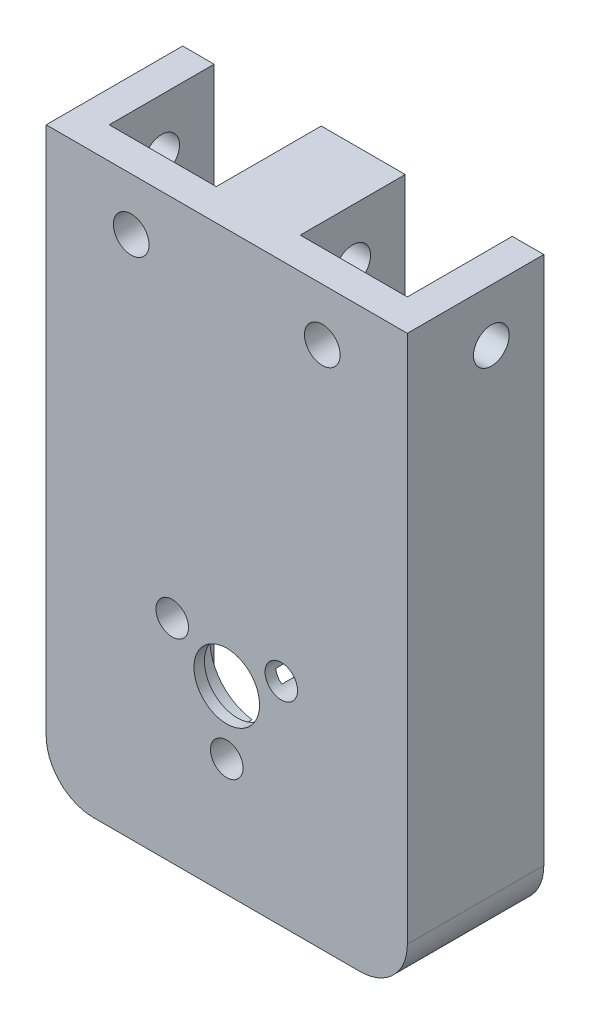
SolidWorks part; units mm, degrees
ref_plane "Front Plane" through (0, 0, 0) normal (0, 0, 1) x (1, 0, 0)
ref_plane "Top Plane" through (0, 0, 0) normal (0, 1, 0) x (1, 0, 0)
ref_plane "Right Plane" through (0, 0, 0) normal (1, 0, 0) x (0, 0, -1)
sketch "Sketch1" plane through (0, 0, 0) normal (0, 0, 1) x (1, 0, 0)
  line L0 (0, 20) -> (0, -20) construction
  line L1 (25, 0) -> (-25, 0) construction
  line L2 (17.2, 1.2765) -> (17.2, 37.7)
  line L3 (17.2, 37.7) -> (14.2, 37.7)
  line L4 (0, 37.7) -> (0, 14.7) construction
  line L5 (0, -14) -> (14.2, -14) construction
  line L6 (-14.2, -14.2) -> (14.2, -14.2)
  line L7 (-17.2, -17.2) -> (17.2, -17.2)
  line L8 (17.2, 1.2765) -> (17.2, -17.2)
  line L9 (14.2, 0) -> (14.2, -14.2)
  line L10 (0, -14) -> (25, -14) construction
  line L11 (0, -14.2) -> (25, -14.2) construction
  line L12 (0, -17.2) -> (25, -17.2) construction
  line L13 (-17.2, 1.2765) -> (-17.2, -17.2)
  line L14 (-14.2, 0) -> (-14.2, -14.2)
  line L15 (-17.2, 1.2765) -> (-17.2, 37.7)
  line L16 (-14.2, 17.7) -> (-4, 17.7)
  line L17 (-14.2, 37.7) -> (-14.2, 17.7)
  line L18 (14.2, 37.7) -> (14.2, 17.7)
  line L19 (-14.2, 37.7) -> (-17.2, 37.7)
  line L20 (0, 17.7) -> (0, 37.7) construction
  line L21 (4, 17.7) -> (4, 37.7)
  line L22 (-4, 17.7) -> (-4, 37.7)
  line L23 (-4, 37.7) -> (4, 37.7)
  line L24 (4, 17.7) -> (14.2, 17.7)
  line L25 (-4, 14.7) -> (-14.2, 14.7)
  line L26 (-14.2, 14.7) -> (-14.2, 0)
  line L27 (4, 14.7) -> (14.2, 14.7)
  line L28 (14.2, 0) -> (14.2, 14.7)
  line L29 (17.2, 12.0941) -> (-17.2, 12.0941) construction
  line L30 (-9.1, 17.7) -> (-9.1, 12.0941) construction
  line L31 (-11.35, 17.7) -> (-11.35, 12.0941) construction
  line L32 (-6.85, 17.7) -> (-6.85, 12.0941) construction
  line L33 (4, 14.7) -> (4, 14.1)
  line L35 (4, 14.1) -> (-4, 14.1)
  line L36 (-4, 14.7) -> (-4, 14.1)
  line L37 (0, 14.7) -> (-4, 14.1) construction
  line L38 (4, 14.1) -> (0, 14.7) construction
  circle A1 centre (0, 0) radius 6 construction
  circle A7 centre (0, 0) radius 14 construction
  arc A9 (0, 17.7) -> (17.2, 1.2765) centre (0.0175, 0.5) cw construction
  point P7 (0, 17.7)
  point P12 (0, 0)
  point P18 (0, 0)
  point P20 (0, 0)
  point P46 (0, 12.0941)
  dimension "D2" = 12
  dimension "D3" = 17.2
  dimension "D6" = 28
  dimension "D8" = 14.2
  dimension "D5" = 20
  dimension "D7" = 25
  dimension "D10" = 10.2
  dimension "D11" = 0.2
  dimension "D13" = 10.2
  dimension "D4" = 14.7
  dimension "D9" = 3
  dimension "D14" = 2.25
  dimension "D16" = 8
  dimension "D17" = 4
  dimension "D18" = 0.6
  dimension "D19" = 20
  dimension "D20" = 54.9
  dimension "D12" = 3
  dimension "D15" = 2.25
extrude "Main Pockets" add sketch "Sketch1" against normal blind 10
sketch "Sketch2" plane through (0, 0, 0) normal (0, 0, 1) x (1, 0, 0)
  line L0 (0, 20) -> (0, -20) construction
  line L1 (-9.1, 17.7) -> (-9.1, 37.7) construction
  line L4 (0, 34) -> (0, 14.2) construction
  line L5 (0, -14) -> (14.2, -14) construction
  line L11 (-17.2, 37.7) -> (-17.2, -17.2)
  line L12 (-17.2, -17.2) -> (17.2, -17.2)
  line L16 (17.2, 37.7) -> (17.2, -17.2)
  line L17 (-4, 17.7) -> (-14.2, 17.7) construction
  line L18 (9.1, 17.7) -> (9.1, 37.7) construction
  line L19 (14.2, 17.7) -> (4, 17.7) construction
  line L21 (-17.2, 32.7) -> (17.2, 32.7) construction
  line L22 (-17.2, 37.7) -> (17.2, 37.7)
  circle A1 centre (0, 0) radius 6 construction
  circle A7 centre (0, 0) radius 14 construction
  arc A9 (0, 17.2) -> (17.2, 0) centre (0, 0) cw construction
  circle A10 centre (0, -6) radius 1.55
  circle A11 centre (-5.1962, 3) radius 1.55
  circle A12 centre (5.1962, 3) radius 1.55
  circle A13 centre (-9.1, 32.7) radius 1.7
  circle A14 centre (9.1, 32.7) radius 1.7
  circle A15 centre (0, 0) radius 3.125
  point P11 (0, 0)
  point P12 (0, 0)
  point P18 (0, 0)
  point P20 (0, 0)
  dimension "D1" = 6.25
  dimension "D2" = 12
  dimension "D3" = 3.1
  dimension "D6" = 28
  dimension "D7" = 3.4
  dimension "D5" = 20
  dimension "D4" = 3
extrude "Mounting Holes" add sketch "Sketch2" along normal blind 3
sketch "Sketch3" plane through (0, 0, 0) normal (0, 0, 1) x (1, 0, 0)
  line L0 (0, 20) -> (0, -20) construction
  line L1 (25, 0) -> (-25, 0) construction
  line L4 (0, 34) -> (0, 14.2) construction
  line L5 (0, -14) -> (14.2, -14) construction
  circle A7 centre (0, 0) radius 14 construction
  arc A9 (0, 17.2) -> (17.2, 0) centre (0, 0) cw construction
  circle A11 centre (0, 0) radius 4.6
  dimension "D2" = 9.2
  dimension "D6" = 28
  dimension "D5" = 20
  dimension "D7" = 25
extrude "Cut-Extrude1" cut sketch "Sketch3" along normal blind 2
sketch "Sketch4" plane through (0, 0, -10) normal (0, 0, -1) x (-1, 0, 0)
  circle A0 centre (-14.2, 17.7) radius 1.5
  circle A1 centre (-4, 17.7) radius 1.5
  circle A2 centre (4, 17.7) radius 1.5
  circle A3 centre (14.2, 17.7) radius 1.5
  dimension "D1" = 3
extrude "Cut-Extrude2" cut sketch "Sketch4" against normal up to surface (10 mm away) up to face at (10.8, 32.7, 0)
sketch "Sketch5" plane through (0, 17.7, 0) normal (0, 1, 0) x (1, 0, 0)
  line L0 (0, 10) -> (0, -3) construction
  line L1 (4, 10) -> (-4, 10) construction
  line L3 (-9.1, 0) -> (-9.1, 10) construction
  line L4 (-12.7, 0) -> (-5.5, 0)
  line L5 (-5.5, 10) -> (-12.7, 10)
  line L6 (-12.7, 0) -> (-5.5, 0) construction
  line L7 (-5.5, 0) -> (-5.5, 10)
  line L9 (-5.5, 10) -> (-12.7, 10) construction
  line L12 (-12.7, 5) -> (-5.5, 5) construction
  line L17 (-5.5, 0) -> (-5.5, 10) construction
  line L18 (-12.7, 10) -> (-12.7, 0)
  line L19 (-12.7, 10) -> (-12.7, 0) construction
  circle A0 centre (-9.1, 5) radius 1.75
  circle A1 centre (9.1, 5) radius 1.75
  dimension "D2" = 3.5
  dimension "D3" = 5
  dimension "D1" = 0
extrude "Cut-Extrude4" cut sketch "Sketch5" against normal up to surface (3 mm away) contours A1 | A0 up to face at (9.1, 14.7, -5)
sketch "Sketch6" plane through (0, -17.2, 0) normal (0, -1, 0) x (1, 0, 0)
  line L0 (12.2, -10) -> (12.2, -2)
  line L1 (12.2, -2) -> (-12.2, -2)
  line L3 (-12.2, -10) -> (12.2, -10)
  line L4 (14.2, 0) -> (4, 0)
  line L5 (4, 0) -> (4, -10)
  line L6 (4, -10) -> (14.2, -10)
  line L7 (14.2, -10) -> (14.2, 0)
  line L10 (4, -10) -> (14.2, -10) construction
  line L11 (14.2, -10) -> (14.2, 0) construction
  line L12 (-14.2, -10) -> (-14.2, 0) construction
  line L13 (-14.2, -10) -> (-14.2, 0) construction
  line L14 (-12.2, -10) -> (-12.2, -2)
  line L15 (12.2, -2) -> (6, -2) construction
  line L16 (4, 0) -> (4, -10) construction
  line L17 (-12.2, -10) -> (-12.2, 0) construction
  line L18 (6, -2) -> (6, -10) construction
  line L23 (14.2, 0) -> (4, 0) construction
  line L24 (14.2, 0) -> (4, 0) construction
  circle A0 centre (-9.1, -5) radius 1.75 construction
  circle A1 centre (9.1, -5) radius 1.75 construction
  circle A2 centre (-9.1, -5) radius 1.75 construction
  circle A3 centre (9.1, -5) radius 1.75 construction
  dimension "D3" = 2
  dimension "D1" = 0
  dimension "Offset" = 2
extrude "Cut-Extrude6" cut sketch "Sketch6" against normal up to surface (3 mm away) up to face at (0, -14.2, -5)
sketch "Sketch8" plane through (17.2, 0, 0) normal (1, 0, 0) x (0, 0, -1)
  line L0 (0, 19.2) -> (0, 37.7) construction
  line L1 (0, 19.2) -> (0, 37.7) construction
  line L2 (-3, 37.7) -> (10, 37.7) construction
  line L3 (5, 19.2) -> (5, 37.7) construction
  line L4 (-3, 32.7) -> (10, 32.7) construction
  circle A0 centre (5, 32.7) radius 1.7
  dimension "D2" = 3.4
  dimension "D1" = 5
extrude "Cut-Extrude7" cut sketch "Sketch8" against normal through all
fillet "Fillet1" radius 1.5 6 edges at (-4, 14.7, -5) (4, 14.7, -5) (-14.2, -14.2, -5) (-14.2, 14.7, -5) (14.2, 14.7, -5) (14.2, -14.2, -5)
fillet "Fillet2" radius 4.5 2 edges at (17.2, -17.2, -3.5) (-17.2, -17.2, -3.5)
fillet "Fillet3" radius 3 2 edges at (-12.2, -15.7, -2) (12.2, -15.7, -2)
